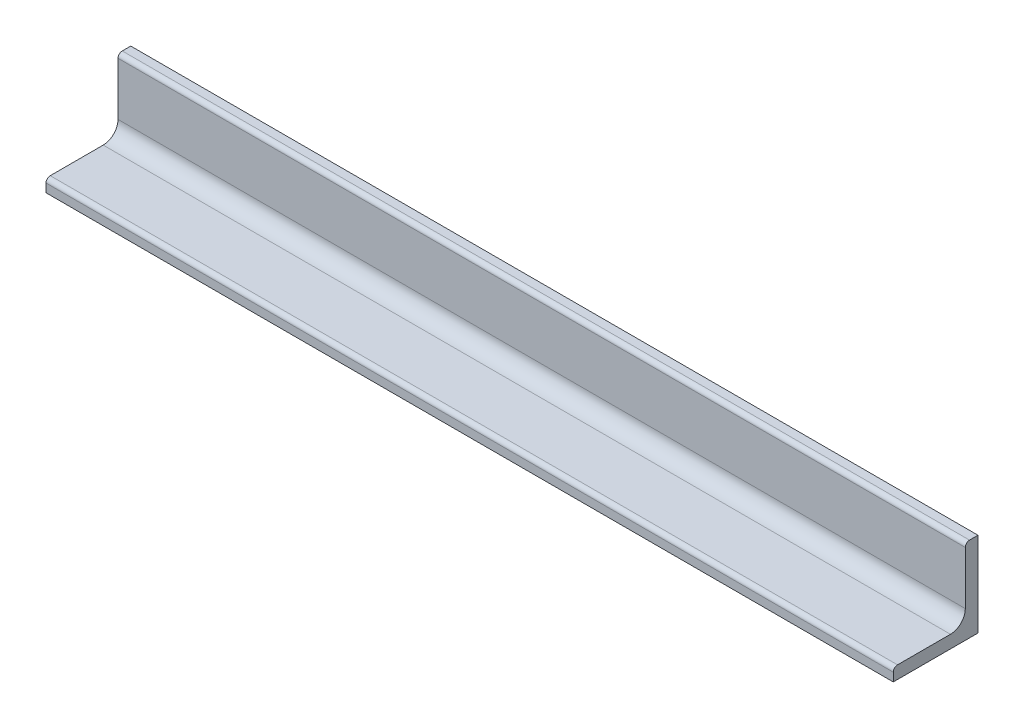
SolidWorks part; units mm, degrees
ref_plane "Front" through (0, 0, 0) normal (0, 0, 1) x (1, 0, 0)
ref_plane "Top" through (0, 0, 0) normal (0, 1, 0) x (1, 0, 0)
ref_plane "Right" through (0, 0, 0) normal (1, 0, 0) x (0, 0, -1)
sketch "Sketch1" plane through (0, 0, 0) normal (1, 0, 0) x (0, 1, 0)
  line L0 (0, 20) -> (0, 0)
  line L1 (0, 0) -> (20, 0)
  line L2 (3, 19) -> (3, 6.5)
  line L3 (6.5, 3) -> (19, 3)
  line L4 (0, 20) -> (2, 20)
  line L5 (20, 0) -> (20, 2)
  arc A0 (2, 20) -> (3, 19) centre (2, 19) cw
  arc A1 (20, 2) -> (19, 3) centre (19, 2) ccw
  arc A2 (3, 6.5) -> (6.5, 3) centre (6.5, 6.5) ccw
extrude "Base" add sketch "Sketch1" along normal blind 200
equation "\"r1@Sketch1\" = \"d@Sketch1\" / 3"
equation "\"d1@Sketch1\" = \"d@Sketch1\""
equation "\"b1@Sketch1\" = \"b@Sketch1\""
